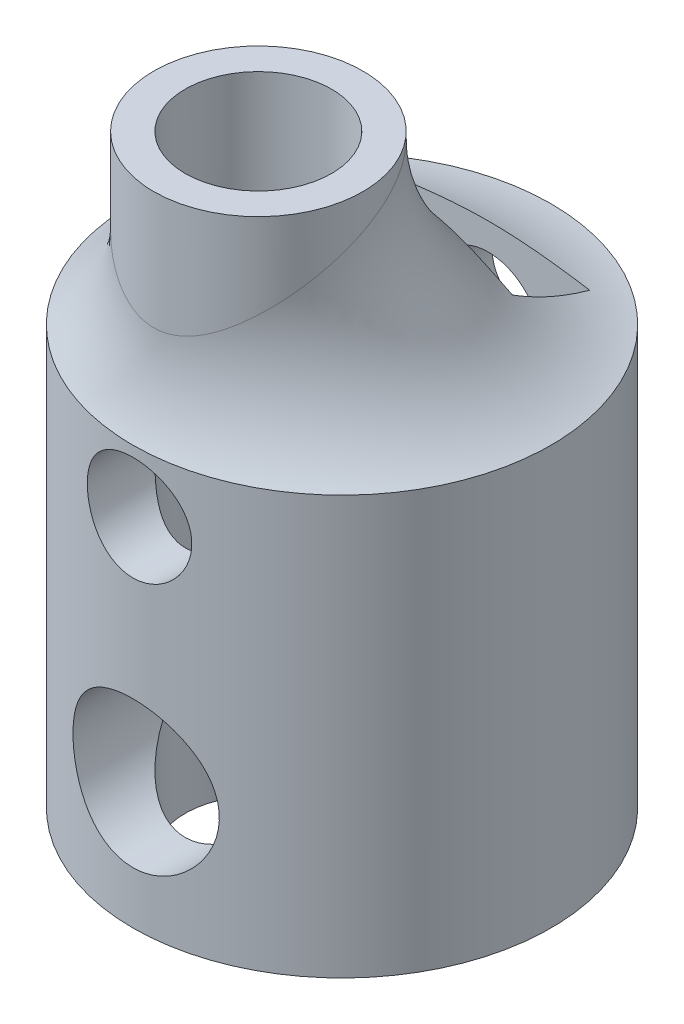
SolidWorks part; units mm, degrees
ref_plane "Alzado" through (0, 0, 0) normal (0, 0, 1) x (1, 0, 0)
ref_plane "Planta" through (0, 0, 0) normal (0, 1, 0) x (1, 0, 0)
ref_plane "Vista lateral" through (0, 0, 0) normal (1, 0, 0) x (0, 0, -1)
sketch "Croquis1" plane through (0, 0, 0) normal (0, 1, 0) x (1, 0, 0)
  circle A0 centre (0, 0) radius 10
  dimension "D1" = 20
extrude "Saliente-Extruir1" add sketch "Croquis1" along normal blind 20
sketch "Croquis2" plane through (0, 20, 0) normal (0, 1, 0) x (1, 0, 0)
  line L0 (0, -4) -> (0, 10) construction
  circle A0 centre (0, -4) radius 5
  circle A2 centre (0, 0) radius 10 construction
  dimension "D1" = 10
  dimension "D2" = 14
extrude "Saliente-Extruir2" add sketch "Croquis2" along normal blind 10
fillet "Redondeo1" radius 10 1 edges at (0, 20, 9)
sketch "Croquis3" plane through (0, 30, 0) normal (0, 1, 0) x (1, 0, 0)
  line L0 (0, -4) -> (0, 10) construction
  circle A0 centre (0, -4) radius 3.5
  circle A1 centre (0, 0) radius 10 construction
  dimension "D1" = 7
  dimension "D2" = 14
extrude "Cortar-Extruir1" cut sketch "Croquis3" against normal up to next
ref_plane "Plano1" through (10, 0, 0) normal (1, 0, 0) x (0, 0, -1)
ref_plane "Plano2" through (0, 0, -10) normal (0, 0, -1) x (-1, 0, 0)
sketch "Croquis5" plane through (0, 0, -10) normal (0, 0, -1) x (-1, 0, 0)
  line L0 (0, 0) -> (0, 6) construction
  line L1 (-10, 20) -> (10, 20) construction
  line L2 (-10, 20) -> (-10, 0) construction
  line L3 (-10, 0) -> (10, 0) construction
  line L4 (10, 20) -> (10, 0) construction
  line L5 (10, 10) -> (7.7498, 10) construction
  line L6 (0, 17) -> (0, 20) construction
  circle A0 centre (0, 6) radius 3.5
  circle A1 centre (0, 17) radius 2.5
  dimension "D2" = 7
  dimension "D3" = 5
  dimension "D1" = 6
  dimension "D4" = 3
extrude "Cortar-Extruir3" cut sketch "Croquis5" against normal through all
sketch "Croquis6" plane through (0, 0, 0) normal (0, -1, 0) x (1, 0, 0)
  line L0 (0, -10) -> (0, -7) construction
  line L1 (0, -7) -> (0, -3.3) construction
  line L2 (-4.85, -7) -> (-4.85, -3.3)
  line L3 (4.85, -7) -> (-4.85, -7)
  line L4 (4.85, -7) -> (4.85, -3.3)
  line L5 (4.85, -3.3) -> (-4.85, -3.3)
  circle A0 centre (0, 0) radius 10 construction
  dimension "D1" = 3
  dimension "D3" = 3.7
  dimension "D4" = 4.85
extrude "Cortar-Extruir4" cut sketch "Croquis6" against normal up to next
